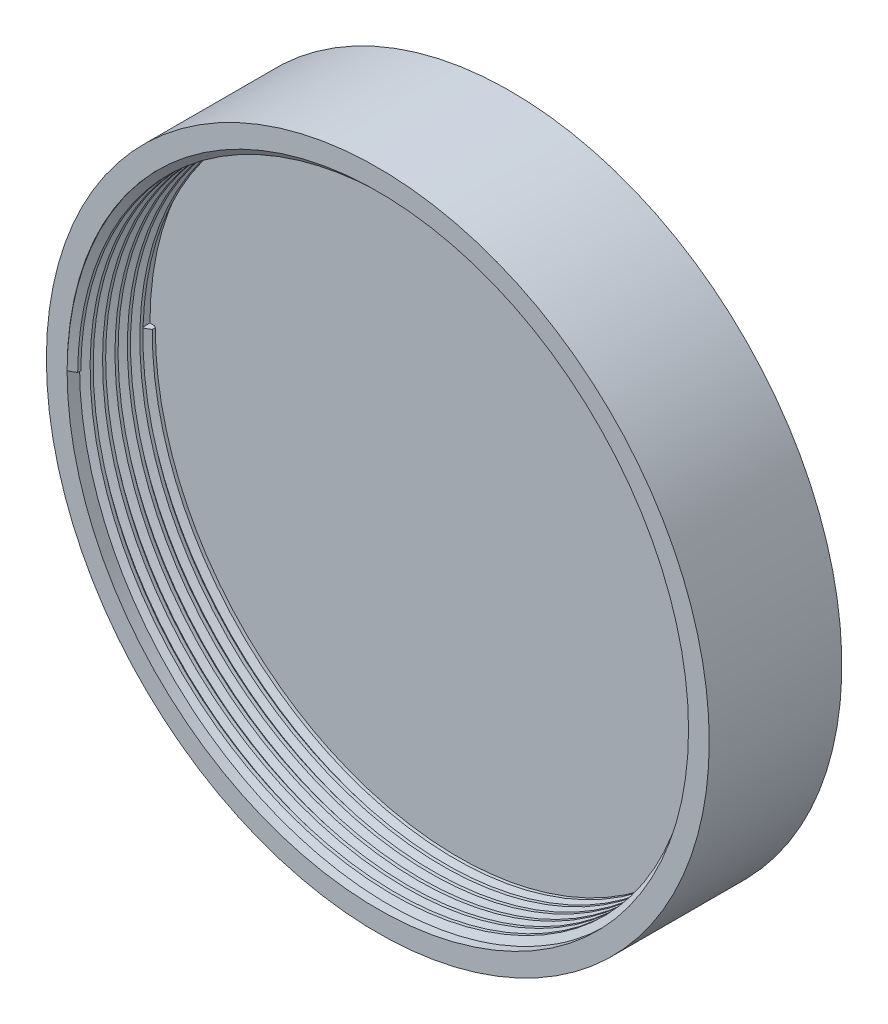
SolidWorks part; units mm, degrees
material "1060-H12"
ref_plane "Front Plane" through (0, 0, 0) normal (0, 0, 1) x (1, 0, 0)
ref_plane "Top Plane" through (0, 0, 0) normal (0, 1, 0) x (1, 0, 0)
ref_plane "Right Plane" through (0, 0, 0) normal (1, 0, 0) x (0, 0, -1)
sketch "Szkic1" plane through (0, 0, 0) normal (0, 0, 1) x (1, 0, 0)
  circle A0 centre (0, 0) radius 80
  dimension "D1" = 160
extrude "Dodanie-wyciągnięcie1" add sketch "Szkic1" along normal blind 30 contours A0
sketch "Szkic2" plane through (0, 0, 30) normal (0, 0, 1) x (1, 0, 0)
  circle A1 centre (0, 0) radius 75
  point P0 (0, 0)
  dimension "D1" = 150
extrude "Wytnij-wyciągnięcie2" cut sketch "Szkic2" against normal blind 20 contours A1
sketch "Szkic20" plane through (0, 0, 0) normal (0, 0, -1) x (-1, 0, 0)
  circle A1 centre (0, 0) radius 80
  circle A2 centre (0, 0) radius 80
  dimension "D1" = 0
extrude "Dodanie-wyciągnięcie2" add sketch "Szkic20" along normal blind 22
sketch "Szkic21" plane through (0, 0, 0) normal (0, 1, 0) x (1, 0, 0)
  line L0 (75, -30) -> (-75, -30) construction
  line L1 (-75, -30) -> (-80, -30) construction
  line L2 (-80, -30) -> (-80, 20) construction
  line L4 (80, 20) -> (80, -30) construction
  line L5 (80, -30) -> (75, -30) construction
  line L6 (0, 0) -> (0, -50000) construction
  line L7 (75, -30) -> (-75, -30)
  line L8 (0, 22) -> (-13.9951, 22)
  line L9 (-13.9951, 22) -> (-10.6003, 20.04)
  line L10 (-10.6003, 20.04) -> (-5, 10.34)
  line L11 (-5, 10.34) -> (-5, -2.46)
  line L12 (-5, -2.46) -> (0, -7.46)
  line L13 (0, 22) -> (0, -7.46)
  line L14 (-75, -30) -> (-80, -30)
  line L15 (-80, -30) -> (-80, 22)
  line L16 (-80, 22) -> (80, 22) construction
  line L17 (80, 22) -> (80, -30)
  line L18 (80, -30) -> (75, -30)
  dimension "D1" = 12.8
  dimension "D2" = 1.96
  dimension "D3" = 5
  dimension "D4" = 30
  dimension "D5" = 29.46
  dimension "D6" = 60
  dimension "D7" = 45
  dimension "D8" = 13.9951
revolve "Wycięcie-obrót1" cut sketch "Szkic21" angle 360 about L6 region at (-3.6181, 0, -10.7879)
sketch "Szkic22" plane through (0, 0, -22) normal (0, 0, -1) x (-1, 0, 0)
  circle A0 centre (0, 0) radius 35
  circle A1 centre (0, 0) radius 80 construction
  circle A2 centre (0, 0) radius 80
  dimension "D1" = 70
extrude "Wytnij-wyciągnięcie3" cut sketch "Szkic22" against normal blind 20
thread "Gwint1" pitch 3 method extrude profile "Thread Profile2" start angle 0, offset 0, length 18, pitch 3, diameter 150
cosmetic thread "Oznaczenie gwintu1" parameters "D2"=151
ref_plane "Płaszczyzna2" through (-75, 0, 30) normal (0, -1, 0) x (-1, 0, 0)
sketch "Thread Profile2" plane through (-75, 0, 30) normal (0, -1, 0) x (-1, 0, 0)
  line L0 (0, 0) -> (0, 3) construction
  line L11 (0, 0) -> (0, 2.625)
  line L12 (0, 2.625) -> (-1.6238, 1.6875)
  line L13 (-1.6238, 1.6875) -> (-1.6238, 0.9375)
  line L15 (-1.6238, 0.9375) -> (0, 0)
  line L17 (-1.6238, 1.3125) -> (0, 1.3125) construction
  point P2 (0, 0)
  dimension "Pitch" = 3
  dimension "Profile_Angle" = 60
  dimension "Profile_Land" = 0.75
  dimension "Profile_Height" = 1.6238
